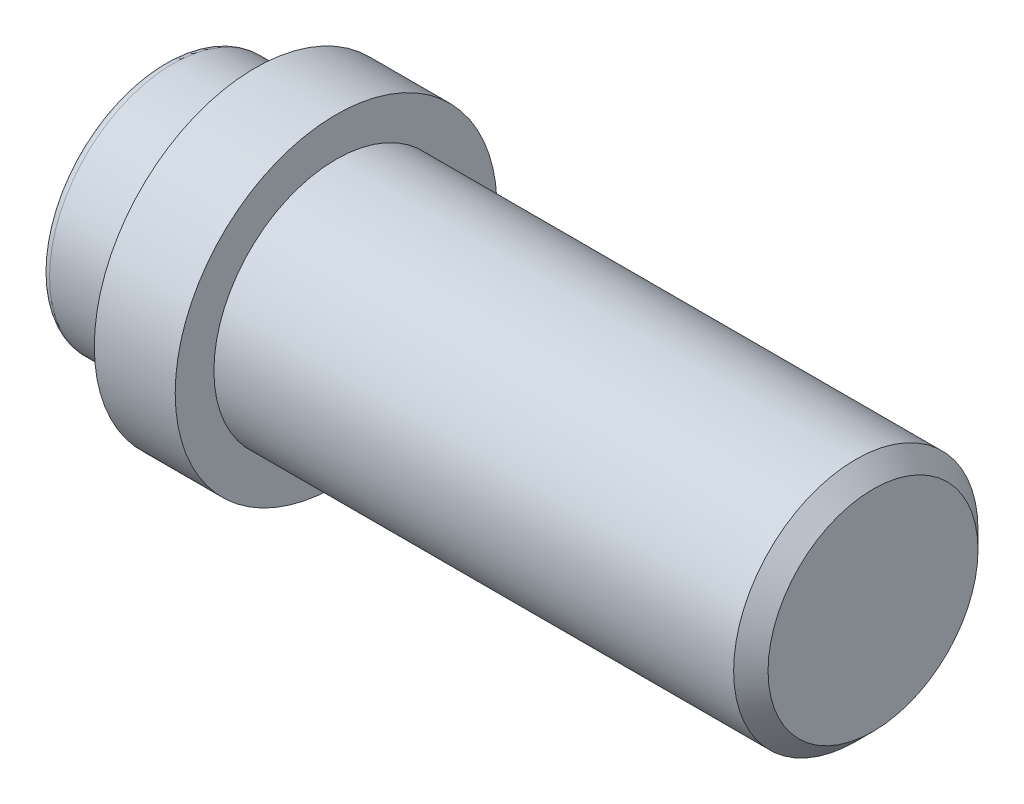
SolidWorks part; units mm, degrees
material "Brass Alloy 360"
ref_plane "Front Plane" through (0, 0, 0) normal (0, 0, 1) x (1, 0, 0)
ref_plane "Top Plane" through (0, 0, 0) normal (0, 1, 0) x (1, 0, 0)
ref_plane "Right Plane" through (0, 0, 0) normal (1, 0, 0) x (0, 0, -1)
sketch "Sketch1" plane through (0, 0, 0) normal (0, 0, 1) x (1, 0, 0)
  line L0 (0.127, 1.8161) -> (1.3462, 1.8161)
  line L1 (0, 0) -> (0, 1.6891)
  line L2 (0, 0) -> (10.4648, 0)
  line L3 (10.4648, 1.5494) -> (10.4648, 0)
  line L4 (10.2108, 1.8034) -> (10.4648, 1.5494)
  line L5 (2.54, 1.8034) -> (10.2108, 1.8034)
  line L6 (2.54, 2.3749) -> (2.54, 1.8034)
  line L7 (1.3462, 2.3749) -> (2.54, 2.3749)
  line L8 (1.3462, 1.8161) -> (1.3462, 2.3749)
  line L9 (0, 0) -> (10.4648, 0) construction
  arc A0 (0.127, 1.8161) -> (0, 1.6891) centre (0.127, 1.6891) ccw
  dimension "D7" = 45
revolve "RevolutionAngle1" add sketch "Sketch1" angle 360 about L9
hole_wizard "Hole1" positions "Sketch3" profile "Sketch2" legacy
sketch "Sketch3" plane through (0, 0, 0) normal (-1, 0, 0) x (0, 0, 1)
  point P0 (0, 0)
sketch "Sketch2" plane through (0, 0, 0) normal (0, 1, 0) x (0, 0, 1)
  line L0 (0, 0) -> (0, 9.4525)
  line L1 (0, 9.4525) -> (1.3589, 8.636)
  line L2 (1.3589, 8.636) -> (1.3589, 0.242)
  line L3 (1.3589, 0.242) -> (1.4986, 0)
  line L4 (1.4986, 0) -> (0, 0)
  line L5 (0, -14.3089) -> (0, 102.4216) construction
  line L6 (0, 9.4525) -> (-1.3589, 8.636) construction
  line L7 (-1.3589, 0.242) -> (-1.4986, 0) construction
  dimension "Diameter" = 2.7178
  dimension "Depth" = 8.636
  dimension "C-Sink Diameter" = 2.9972
  dimension "C-Sink Angle" = 60
  dimension "Drill Angle" = 118
ref_axis "Axis1" through (-1.1833, 0, 0) along (1, 0, 0)
